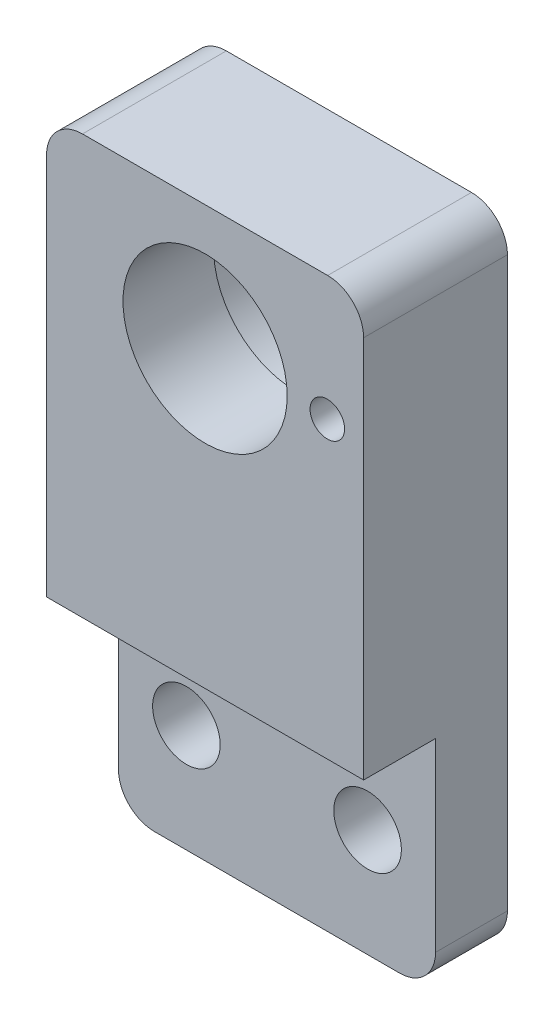
SolidWorks part; units mm, degrees
note: The reader was unsure of these and kept them because the rebuilt part matched: shared geometry of "Sketch1<3>", "Sketch1<4>".
ref_plane "Front Plane" through (0, 0, 0) normal (0, 0, 1) x (1, 0, 0)
ref_plane "Top Plane" through (0, 0, 0) normal (0, 1, 0) x (1, 0, 0)
ref_plane "Right Plane" through (0, 0, 0) normal (1, 0, 0) x (0, 0, -1)
sketch "Sketch1" plane through (0, 0, 0) normal (0, 0, 1) x (1, 0, 0)
  line L85 (128.543, 64.1852) -> (150.193, 64.1852)
  line L86 (125.368, 67.3602) -> (125.368, 117.5403)
  line L87 (125.368, 83.7153) -> (153.368, 83.7153)
  line L88 (153.368, 67.3602) -> (153.368, 117.5403)
  line L89 (150.193, 120.7153) -> (128.543, 120.7153)
  circle A99 centre (139.368, 109.7153) radius 7.9502
  circle A100 centre (139.368, 109.7153) radius 7.25
  arc A101 (125.368, 67.3602) -> (128.543, 64.1852) centre (128.543, 67.3602) ccw
  arc A102 (150.193, 64.1852) -> (153.368, 67.3602) centre (150.193, 67.3602) ccw
  arc A103 (153.368, 117.5403) -> (150.193, 120.7153) centre (150.193, 117.5403) ccw
  arc A104 (128.543, 120.7153) -> (125.368, 117.5403) centre (128.543, 117.5403) ccw
  circle A105 centre (131.368, 73.7153) radius 2.9845
  circle A106 centre (147.368, 73.7153) radius 2.9845
  circle A107 centre (150.163, 109.7153) radius 1.524
extrude "Boss-Extrude1" add sketch "Sketch1" along normal blind 12.7 contours L89 A104 L86 L87 L88 A103 A107 A99 | L85 A102 L88 L87 L86 A101 A106 A105 | A99 A100
extrude "Cut-Extrude1" cut sketch "Sketch1<3>" along normal blind 4.699 contours A99 A100
sketch "Sketch1<3>" plane through (0, 0, 0) normal (0, 0, 1) x (1, 0, 0) same geometry as "Sketch1"
extrude "Cut-Extrude2" cut sketch "Sketch1<4>" against normal blind 6.35 from offset 12.7 contours L85 A102 L88 L87 L86 A101 A106 A105
sketch "Sketch1<4>" plane through (0, 0, 0) normal (0, 0, 1) x (1, 0, 0) same geometry as "Sketch1"
